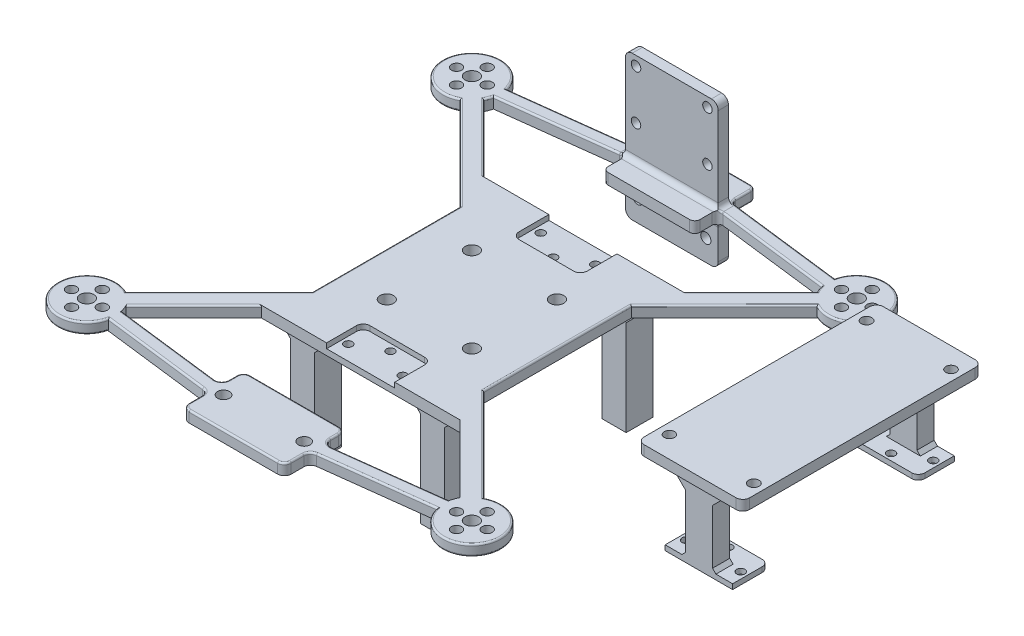
SolidWorks part; units mm, degrees
ref_plane "Front Plane" through (0, 0, 0) normal (0, 0, 1) x (1, 0, 0)
ref_plane "Top Plane" through (0, 0, 0) normal (0, 1, 0) x (1, 0, 0)
ref_plane "Right Plane" through (0, 0, 0) normal (1, 0, 0) x (0, 0, -1)
sketch "Sketch1" plane through (0, 0, 0) normal (0, 1, 0) x (1, 0, 0)
  line L10 (25.2228, 21.7178) -> (52.5194, 49.0143)
  line L11 (29.1718, 32.6991) -> (49.0032, 52.5305)
  line L14 (25.2228, -21.7245) -> (52.5163, -49.018)
  line L15 (29.1386, -32.6991) -> (48.9964, -52.5569)
  line L19 (-25.2228, 21.7178) -> (-52.5879, 49.0829)
  line L20 (-29.1386, -32.6991) -> (-49.0885, -52.649)
  line L22 (-25.2228, -21.7245) -> (-52.6084, -49.1101)
  line L33 (-25.2228, -21.7245) -> (-25.2228, 21.7178)
  line L34 (-16.8093, -62.3977) -> (-48.3224, -58.53)
  line L37 (-8.5504, -52.1195) -> (8.5504, -52.1195)
  line L41 (-17.2966, -58.4661) -> (-48.3352, -54.6566)
  line L42 (25.2228, -21.7245) -> (25.2228, 21.7178)
  line L43 (-48.2996, 54.661) -> (-15.2357, 58.719)
  line L44 (17.1959, -58.4785) -> (48.2122, -54.6717)
  line L45 (16.7086, -62.4101) -> (48.2307, -58.5412)
  line L46 (-29.1718, 32.6991) -> (29.1718, 32.6991)
  line L47 (-29.1386, -32.6991) -> (29.1386, -32.6991)
  line L48 (14.7695, 62.6481) -> (48.2209, 58.5424)
  line L49 (15.135, 58.7314) -> (48.2038, 54.6727)
  line L50 (-13.553, 57.2302) -> (-13.553, 53.6195)
  line L51 (-13.553, 64.1245) -> (-13.553, 68.595)
  line L52 (13.4522, 57.2426) -> (13.4522, 53.6195)
  line L53 (-12.053, 52.1195) -> (11.9522, 52.1195)
  line L54 (-15.053, -56.481) -> (-15.053, -54.1195)
  line L55 (-49.0752, 52.6025) -> (-29.1718, 32.6991)
  line L56 (14.9522, -64.3952) -> (14.9522, -68.095)
  line L57 (-14.8702, 62.6357) -> (-48.3224, 58.53)
  line L58 (12.9522, -70.095) -> (-13.053, -70.095)
  line L64 (-12.053, 70.095) -> (11.9522, 70.095)
  line L65 (13.4522, 68.595) -> (13.4522, 64.1369)
  line L66 (-15.053, -68.095) -> (-15.053, -64.3828)
  line L67 (14.9522, -56.4934) -> (14.9522, -54.1195)
  line L68 (12.9522, -52.1195) -> (-13.053, -52.1195)
  line L69 (14.9522, -52.1195) -> (14.9522, -58.7538)
  arc A0 (-52.6084, -49.1101) -> (-48.3224, -58.53) centre (-56.6207, -56.6207) ccw
  arc A1 (52.5194, 49.0143) -> (48.2209, 58.5424) centre (56.5594, 56.5706) ccw
  arc A2 (-49.0752, 52.6025) -> (-48.2996, 54.661) centre (-56.6207, 56.6207) ccw
  arc A3 (48.9964, -52.5569) -> (48.2122, -54.6717) centre (56.5667, -56.5667) ccw
  arc A8 (-48.3352, -54.6566) -> (-49.0885, -52.649) centre (-56.6207, -56.6207) ccw
  arc A9 (48.2307, -58.5412) -> (52.5163, -49.018) centre (56.5667, -56.5667) ccw
  arc A11 (13.4522, 64.1369) -> (14.7695, 62.6481) centre (14.9522, 64.1369) ccw
  arc A12 (15.135, 58.7314) -> (13.4522, 57.2426) centre (14.9522, 57.2426) ccw
  arc A13 (-13.553, 64.1245) -> (-14.8702, 62.6357) centre (-15.053, 64.1245) cw
  arc A14 (-49.0752, 52.6025) -> (-48.2996, 54.661) centre (-56.6207, 56.6207) ccw
  arc A15 (48.2038, 54.6727) -> (49.0032, 52.5305) centre (56.5594, 56.5706) ccw
  arc A16 (-48.2888, 58.5341) -> (-52.5879, 49.0829) centre (-56.6207, 56.6207) ccw
  arc A17 (14.9522, -56.4934) -> (17.1959, -58.4785) centre (16.9522, -56.4934) ccw
  arc A20 (16.7086, -62.4101) -> (14.9522, -64.3952) centre (16.9522, -64.3952) ccw
  arc A21 (-15.2357, 58.719) -> (-13.553, 57.2302) centre (-15.053, 57.2302) cw
  arc A22 (-13.553, 53.6195) -> (-12.053, 52.1195) centre (-12.053, 53.6195) ccw
  arc A23 (11.9522, 52.1195) -> (13.4522, 53.6195) centre (11.9522, 53.6195) ccw
  arc A24 (11.9522, 70.095) -> (13.4522, 68.595) centre (11.9522, 68.595) cw
  arc A25 (-12.053, 70.095) -> (-13.553, 68.595) centre (-12.053, 68.595) ccw
  arc A26 (-15.053, -56.481) -> (-17.2966, -58.4661) centre (-17.053, -56.481) cw
  arc A27 (-15.053, -64.3828) -> (-16.8093, -62.3977) centre (-17.053, -64.3828) ccw
  arc A28 (-13.053, -70.095) -> (-15.053, -68.095) centre (-13.053, -68.095) cw
  arc A29 (12.9522, -70.095) -> (14.9522, -68.095) centre (12.9522, -68.095) ccw
  arc A30 (14.9522, -54.1195) -> (12.9522, -52.1195) centre (12.9522, -54.1195) ccw
  arc A31 (-15.053, -54.1195) -> (-13.053, -52.1195) centre (-13.053, -54.1195) cw
  point P10 (0, 0)
  point P34 (14.9522, -62.6256)
  point P37 (-15.053, -58.7415)
  point P44 (-28.9553, -58.9711)
  point P57 (13.4522, 58.9379)
  dimension "D1" = 2
  dimension "D2" = 1.5
extrude "Boss-Extrude1" add sketch "Sketch1" along normal blind 3.25 contours A16 L19 L33 L22 A0 L34 L45 A9 L14 L42 L10 A1 L48 L50 L57 L49 A15 L11 L46 L55 A2 L43 A13 L41 A8 L20 L47 L15 A3 L44 L37 region at (0.0088, 0, 0.3906)
sketch "Sketch2" plane through (0, 3.25, 0) normal (0, 1, 0) x (1, 0, 0)
  circle A0 centre (-56.6207, 56.6207) radius 2.003
  circle A1 centre (56.6207, 56.6207) radius 2.003
  circle A2 centre (56.6207, -56.6274) radius 2.003
  circle A3 centre (-56.6207, -56.6274) radius 2.003
  circle A6 centre (56.6207, 61.1356) radius 1.498
  circle A7 centre (61.1356, 56.6207) radius 1.495
  circle A8 centre (56.6207, 52.1058) radius 1.5029
  circle A9 centre (52.1058, 56.6207) radius 1.5021
  circle A10 centre (-56.6207, 61.1356) radius 1.498
  circle A11 centre (-52.1058, 56.6207) radius 1.5021
  circle A12 centre (-56.6207, 52.1058) radius 1.5029
  circle A13 centre (-61.1356, 56.6207) radius 1.495
  circle A14 centre (56.6207, -61.1356) radius 1.498
  circle A15 centre (52.1058, -56.6207) radius 1.5021
  circle A16 centre (56.6207, -52.1058) radius 1.5029
  circle A17 centre (61.1356, -56.6207) radius 1.495
  circle A18 centre (-56.6207, -61.1356) radius 1.498
  circle A19 centre (-52.1058, -56.6207) radius 1.5021
  circle A20 centre (-61.1356, -56.6207) radius 1.495
  circle A21 centre (-56.6207, -52.1058) radius 1.5029
  circle A22 centre (-12.2493, 12.2453) radius 1.9968
  circle A23 centre (-12.2493, -12.7715) radius 1.9976
  circle A24 centre (12.7793, -12.7715) radius 1.9993
  circle A25 centre (12.7793, 12.2453) radius 2.0015
extrude "Cut-Extrude1" cut sketch "Sketch2" against normal through all
sketch "Sketch4" plane through (0, 3.25, 0) normal (0, 1, 0) x (1, 0, 0)
  line L8 (-13.885, 59.0576) -> (13.4118, 59.0576)
  line L9 (-13.885, 59.0576) -> (-13.885, 62.0613)
  line L10 (-13.885, 62.0613) -> (13.4118, 62.0613)
  line L11 (13.4118, 59.0576) -> (13.4118, 62.0613)
extrude "Boss-Extrude3" add sketch "Sketch4" along normal blind 27 and the other way blind 15.5
fillet "Fillet2" radius 1.5 6 edges at (-0.2366, 0, -59.0576) (13.4118, 3.25, -60.5595) (-0.2366, 3.25, -59.0576) (-13.885, 3.25, -60.5595) (-13.885, 0, -60.5595) (13.4118, 0, -60.5595)
fillet "Fillet3" radius 2 4 edges at (13.4118, -12.25, -60.5595) (-13.885, -12.25, -60.5595) (13.4118, 30.25, -60.5595) (-13.885, 30.25, -60.5595)
sketch "Sketch5" plane through (0, 0, -62.0613) normal (0, 0, -1) x (-1, 0, 0)
  circle A7 centre (-9.7641, -6) radius 1.4993
  circle A8 centre (10.2386, -6) radius 1.4966
  circle A9 centre (-10.2398, 27.5046) radius 1.3963
  circle A10 centre (-10.2398, 13.0011) radius 1.3933
  circle A11 centre (10.7726, 13.0011) radius 1.3992
  circle A12 centre (10.7726, 27.5046) radius 1.4031
extrude "Cut-Extrude2" cut sketch "Sketch5" against normal up to next
fillet "Fillet6" radius 0.5 61 edges at (-14.7161, 3.4074, -58.6919) (-15.3102, 3.2519, -58.7099) (14.5178, 3.3027, -58.6783) (15.0236, 3.25, -58.7409) (32.7041, 3.25, 56.5751) (-0.0504, 3.25, 52.1195) (32.4696, 3.25, 60.4757) (-31.5795, 0, -60.5849) (-13.9296, 0, -63.1306) (-13.553, 0, -66.3598) (-13.1136, 0, -69.6557) (31.4952, 0, -60.5953) (13.8288, 0, -63.1429) (13.4522, 0, -66.366) (13.0129, 0, -69.6557) (-31.5795, 3.25, -60.5849) (-13.9296, 3.25, -63.1306) (-13.553, 3.25, -66.3598) (-13.1136, 3.25, -69.6557) (-0.0504, 3.25, -70.095) (13.0129, 3.25, -69.6557) (13.4522, 3.25, -66.366) (13.8288, 3.25, -63.1429) (-31.8423, 3.25, -56.6808) (-48.6209, 3.25, -53.6067) (31.6694, 3.25, -56.7021) (48.5317, 3.25, -53.5748) (39.0875, 3.25, -42.6148) (-39.1235, 3.25, -42.6508) (38.8711, 3.25, -35.366) (25.2228, 3.25, 0.0034) (38.8696, 3.25, 35.3713) (64.3788, 0, 60.0823) (64.3788, 3.25, 60.0823) (-39.1136, 3.25, 42.674) (-32.8159, 3.25, 56.5614) (-32.5659, 3.25, 60.4638) (-64.3713, 0, 60.1472) (-64.3713, 3.25, 60.1472) (-38.9156, 3.25, 35.4173) (-25.2228, 3.25, 0.0034) (-38.9054, 3.25, -35.4003) (-64.4022, 3.25, -60.1603) (-64.4022, 0, -60.1603) (64.3699, 0, -60.0942) (-0.0504, 0, -70.095) (31.4952, 3.25, -60.5953) (64.3699, 3.25, -60.0942) (15.627, 3.25, 57.9912) (14.9522, 3.25, 55.3064) (14.3664, 3.25, 52.7053) (-14.4672, 3.25, 52.7053) (-15.053, 3.25, 55.3003) (-15.7277, 3.25, 57.9789) (15.4544, 3.25, 63.0699) (14.9522, 3.25, 66.2451) (14.3664, 3.25, 69.5092) (-0.0504, 3.25, 70.095) (-14.4672, 3.25, 69.5092) (-15.053, 3.25, 66.2389) (-15.5551, 3.25, 63.0575)
sketch "Sketch6" plane through (0, 3.25, 0) normal (0, 1, 0) x (1, 0, 0)
  line L4 (10.0048, -23.9249) -> (10.0048, -32.6991)
  line L5 (-29.8789, 32.6991) -> (29.8789, 32.6991) construction
  line L6 (10.0048, -32.6991) -> (-10.0395, -32.6991)
  line L7 (-10.0395, -32.6991) -> (-10.0395, -23.9249)
  line L8 (-8.0395, -21.9249) -> (8.0048, -21.9249)
  line L10 (-8.0395, 21.9249) -> (8.0048, 21.9249)
  line L11 (10.0048, 23.9249) -> (10.0048, 32.6991)
  line L12 (10.0048, 32.6991) -> (-10.0395, 32.6991)
  line L13 (-10.0395, 32.6991) -> (-10.0395, 23.9249)
  arc A0 (8.0048, 21.9249) -> (10.0048, 23.9249) centre (8.0048, 23.9249) ccw
  arc A1 (-10.0395, 23.9249) -> (-8.0395, 21.9249) centre (-8.0395, 23.9249) ccw
  arc A2 (8.0048, -21.9249) -> (10.0048, -23.9249) centre (8.0048, -23.9249) cw
  arc A3 (-10.0395, -23.9249) -> (-8.0395, -21.9249) centre (-8.0395, -23.9249) cw
  dimension "D1" = 2
extrude "Cut-Extrude3" cut sketch "Sketch6" against normal blind 1.5
sketch "Sketch7" plane through (0, 1.75, 0) normal (0, 1, 0) x (1, 0, 0)
  circle A0 centre (-8.0479, 28.312) radius 1.205
  circle A1 centre (-0.0173, 23.9294) radius 1.1998
  circle A2 centre (8.0011, 28.312) radius 1.205
  circle A3 centre (8.0011, -28.312) radius 1.205
  circle A4 centre (-0.0173, -23.9294) radius 1.1998
  circle A5 centre (-8.0479, -28.312) radius 1.205
extrude "Cut-Extrude5" cut sketch "Sketch7" against normal through all
sketch "Sketch10" plane through (0, 3.25, 0) normal (0, 1, 0) x (1, 0, 0)
  circle A2 centre (-11.9474, -61.1073) radius 1.7524
  circle A3 centre (11.7714, -61.1073) radius 1.7475
extrude "Cut-Extrude6" cut sketch "Sketch10" against normal through all
sketch "Sketch11" plane through (0, 0, 0) normal (0, 1, 0) x (1, 0, 0)
  line L4 (89.4618, 32.5991) -> (89.4618, 23.9249)
  line L5 (107.4062, 22.0249) -> (91.3618, 22.0249)
  line L6 (109.3062, 32.5991) -> (109.3062, 23.9249)
  line L7 (89.4618, 32.5991) -> (109.3062, 32.5991)
  line L10 (109.3062, -32.5991) -> (109.3062, -23.9249)
  line L11 (107.4062, -22.0249) -> (91.3618, -22.0249)
  line L12 (89.4618, -32.5991) -> (109.3062, -32.5991)
  line L13 (89.4618, -32.5991) -> (89.4618, -23.9249)
  arc A2 (91.3618, 22.0249) -> (89.4618, 23.9249) centre (91.3618, 23.9249) cw
  arc A3 (107.4062, 22.0249) -> (109.3062, 23.9249) centre (107.4062, 23.9249) ccw
  arc A4 (107.4062, -22.0249) -> (109.3062, -23.9249) centre (107.4062, -23.9249) cw
  arc A5 (91.3618, -22.0249) -> (89.4618, -23.9249) centre (91.3618, -23.9249) ccw
extrude "Boss-Extrude4" add sketch "Sketch11" along normal blind 1.5 separate body
sketch "Sketch12" plane through (0, 1.5, 0) normal (0, 1, 0) x (1, 0, 0)
  circle A0 centre (91.3535, 28.3053) radius 1.205
  circle A1 centre (99.384, 23.9228) radius 1.1998
  circle A2 centre (107.4025, 28.3053) radius 1.205
  circle A3 centre (107.4025, -28.3186) radius 1.205
  circle A4 centre (99.384, -23.9361) radius 1.1998
  circle A5 centre (91.3535, -28.3186) radius 1.205
extrude "Cut-Extrude7" cut sketch "Sketch12" against normal through all
sketch "Sketch13" plane through (0, 1.5, 0) normal (0, 1, 0) x (1, 0, 0)
  line L2 (109.3062, 32.5991) -> (89.4618, 32.5991) construction
  line L7 (95.3874, 32.5991) -> (95.3874, 27.5424)
  line L8 (95.3874, 27.5424) -> (103.3936, 27.5424)
  line L9 (103.3936, 32.5991) -> (103.3936, 27.5424)
  line L15 (103.3936, -32.5991) -> (103.3936, -27.5424)
  line L16 (95.3874, -32.5991) -> (95.3874, -27.5424)
  line L17 (95.3874, -27.5424) -> (103.3936, -27.5424)
  line L18 (95.3874, -32.5991) -> (103.3936, -32.5991)
  line L19 (95.3874, 32.5991) -> (103.3936, 32.5991)
extrude "Boss-Extrude5" add sketch "Sketch13" along normal blind 23.5 and the other way blind 1.253
sketch "Sketch14" plane through (0, 25, 0) normal (0, 1, 0) x (1, 0, 0)
  line L1 (83.8736, 35.1637) -> (83.8736, -35.1882)
  line L2 (83.8736, 35.1637) -> (114.9015, 35.1637)
  line L6 (114.9015, 35.1637) -> (114.9015, -35.1882)
  line L7 (83.8736, -35.1882) -> (114.9015, -35.1882)
extrude "Boss-Extrude6" add sketch "Sketch14" along normal blind 1.5 and the other way blind 1.5
sketch "Sketch15" plane through (0, 26.5, 0) normal (0, 1, 0) x (1, 0, 0)
  circle A4 centre (86.9844, 29.1301) radius 1.546
  circle A5 centre (111.8244, 29.1301) radius 1.5226
  circle A6 centre (86.9844, -28.8874) radius 1.5055
  circle A7 centre (111.8244, -28.8874) radius 1.5537
extrude "Cut-Extrude8" cut sketch "Sketch15" against normal up to next (3 mm away)
chamfer "Chamfer2" distance 1 angle 45 4 edges at (95.3874, 1.5, 30.0707) (95.3874, 1.5, -30.0707) (103.3936, 1.5, -30.0707) (103.3936, 1.5, 30.0707)
chamfer "Chamfer3" distance 5 angle 45 4 edges at (103.3936, 23.5, 30.0707) (95.3874, 23.5, 30.0707) (95.3874, 23.5, -30.0707) (103.3936, 23.5, -30.0707)
fillet "Fillet7" radius 2 4 edges at (83.8736, 25, -35.1637) (114.9015, 25, -35.1637) (114.9015, 25, 35.1882) (83.8736, 25, 35.1882)
sketch "Sketch16" plane through (0, 0, 0) normal (0, -1, 0) x (1, 0, 0)
  line L4 (-15.5568, 22.7297) -> (-22.6855, 22.7297)
  line L5 (-15.5568, 22.7297) -> (-15.5568, 30.6742)
  line L6 (-15.5568, 30.6742) -> (-22.6855, 30.6742)
  line L7 (-22.6855, 22.7297) -> (-22.6855, 30.6742)
  line L8 (15.5222, 22.7297) -> (22.6509, 22.7297)
  line L9 (22.6509, 22.7297) -> (22.6509, 30.6742)
  line L10 (15.5222, 30.6742) -> (22.6509, 30.6742)
  line L11 (15.5222, 22.7297) -> (15.5222, 30.6742)
  line L12 (15.5222, -30.6742) -> (22.6509, -30.6742)
  line L13 (22.6509, -22.7297) -> (22.6509, -30.6742)
  line L14 (15.5222, -22.7297) -> (22.6509, -22.7297)
  line L15 (15.5222, -22.7297) -> (15.5222, -30.6742)
  line L16 (-15.5568, -30.6742) -> (-22.6855, -30.6742)
  line L17 (-22.6855, -22.7297) -> (-22.6855, -30.6742)
  line L18 (-15.5568, -22.7297) -> (-22.6855, -22.7297)
  line L19 (-15.5568, -22.7297) -> (-15.5568, -30.6742)
extrude "Boss-Extrude7" add sketch "Sketch16" along normal blind 31
chamfer "Chamfer4" distance 3 angle 45 8 edges at (22.6509, 0, 26.7019) (-15.5568, 0, 26.7019) (15.5222, 0, 26.7019) (-22.6855, 0, 26.7019) (15.5222, 0, -26.7019) (22.6509, 0, -26.7019) (-15.5568, 0, -26.7019) (-22.6855, 0, -26.7019)
